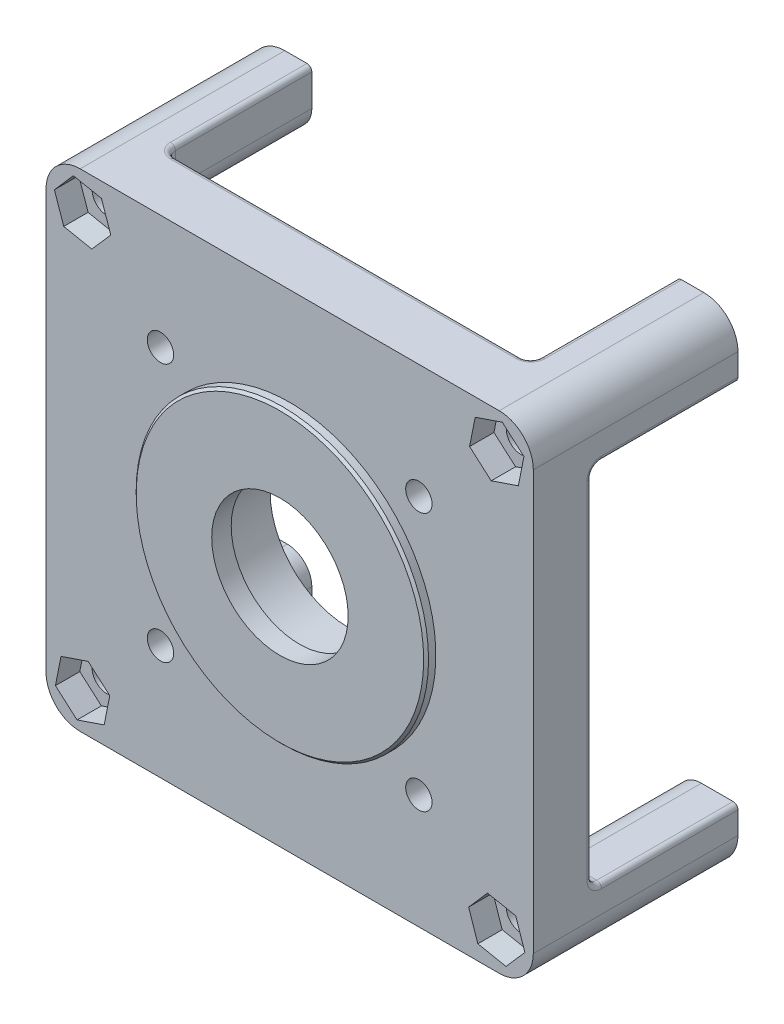
SolidWorks part; units mm, degrees
note: '?' marks a value the reader was unsure of.
ref_plane "Front Plane" through (0, 0, 0) normal (0, 0, 1) x (1, 0, 0)
ref_plane "Top Plane" through (0, 0, 0) normal (0, 1, 0) x (1, 0, 0)
ref_plane "Right Plane" through (0, 0, 0) normal (1, 0, 0) x (0, 0, -1)
ref_axis "Shaft Axis" through (0, 0, -0.635) along (0, 0, 1)?
sketch "Sketch2" plane through (0, 0, 0) normal (0, 0, 1) x (1, 0, 0)
  line L1 (-50, -50) -> (50, -50)
  line L2 (-50, -50) -> (-50, 50)
  line L3 (-50, 50) -> (50, 50)
  line L4 (50, -50) -> (50, 50)
  line L5 (-50, -50) -> (50, 50) construction
  line L6 (-50, 50) -> (50, -50) construction
  point P0 (0, 0)
  dimension "D1" = 100
extrude "Boss-Extrude1" add sketch "Sketch2" along normal blind 12
sketch "Sketch3" plane through (0, 0, 0) normal (0, 0, -1) x (-1, 0, 0)
  circle A0 centre (0, 0) radius 16
  dimension "D1" = 32
extrude "Cut-Extrude1" cut sketch "Sketch3" against normal blind 10
sketch "Sketch14" plane through (0, 0, 12) normal (0, 0, 1) x (1, 0, 0)
  circle A0 centre (0, 0) radius 65
  dimension "D1" = 130
extrude "Cut-Extrude2" [suppressed] cut sketch "Sketch14" against normal blind 2 flip side to cut
hole_wizard "7/16 Clearance Hole1" [suppressed] positions "Sketch7" profile "Sketch8" hole size "7/16" standard "ANSI Inch"
sketch "Sketch7" [suppressed] plane through (0, 0, 10.7) normal (0, 0, 1) x (1, 0, 0)
  line L1 (-58.7375, -58.7375) -> (58.7375, -58.7375) construction
  line L2 (-58.7375, -58.7375) -> (-58.7375, 58.7375) construction
  line L3 (-58.7375, 58.7375) -> (58.7375, 58.7375) construction
  line L4 (58.7375, -58.7375) -> (58.7375, 58.7375) construction
  line L5 (-58.7375, -58.7375) -> (58.7375, 58.7375) construction
  line L6 (-58.7375, 58.7375) -> (58.7375, -58.7375) construction
  line L7 (-76.2, 76.2) -> (76.2, -76.2) construction
  line L8 (76.2, -76.2) -> (76.2, 76.2) construction
  line L9 (76.2, 76.2) -> (-76.2, -76.2) construction
  point P2 (58.7375, 58.7375)
  point P35 (-58.7375, -58.7375)
  point P36 (-58.7375, 58.7375)
  point P37 (58.7375, -58.7375)
  dimension "D1" = 117.475
sketch "Sketch8" plane through (58.7375, 58.7375, 10.7) normal (1, 0, 0) x (0, -1, 0)
  line L0 (0, 0) -> (0, 10.7)
  line L1 (0, 10.7) -> (6.1519, 10.7)
  line L2 (6.1519, 10.7) -> (6.1519, 0)
  line L5 (6.1519, 0) -> (0, 0)
  line L11 (0, -6.35) -> (0, 107.95) construction
  dimension "Thru Hole Dia." = 12.3038
  dimension "Thru Hole Depth" = 10.7
hole_wizard "M6 Clearance Hole1" positions "Sketch13" profile "Sketch12" hole size "M6" standard "ANSI Metric" end condition through all
sketch "Sketch13" plane through (0, 0, 12) normal (0, 0, -1) x (-1, 0, 0)
  line L1 (-42.5, -42.5) -> (42.5, -42.5) construction
  line L2 (-42.5, -42.5) -> (-42.5, 42.5) construction
  line L3 (-42.5, 42.5) -> (42.5, 42.5) construction
  line L4 (42.5, -42.5) -> (42.5, 42.5) construction
  line L5 (-42.5, -42.5) -> (42.5, 42.5) construction
  line L6 (-42.5, 42.5) -> (42.5, -42.5) construction
  line L22 (50, -50) -> (50, 50)
  line L24 (50, 50) -> (-50, -50) construction
  line L26 (-50, 50) -> (50, -50) construction
  line L43 (-50, 50) -> (-50, -50)
  line L44 (-50, 50) -> (-50, -50)
  line L45 (50, 50) -> (-50, 50)
  line L46 (50, 50) -> (-50, 50)
  line L47 (50, -50) -> (50, 50)
  line L48 (50, -50) -> (50, 50)
  line L49 (-50, -50) -> (50, -50)
  line L50 (-50, -50) -> (50, -50)
  point P2 (42.5, 42.5)
  point P61 (-42.5, -42.5)
  point P62 (-42.5, 42.5)
  point P63 (42.5, -42.5)
  dimension "D1" = 85
  dimension "D2" = 0
sketch "Sketch12" plane through (-42.5, 42.5, 12) normal (1, 0, 0) x (0, -1, 0)
  line L0 (0, 0) -> (0, 12)
  line L1 (0, 12) -> (3.05, 12)
  line L2 (3.05, 12) -> (3.05, 0)
  line L5 (3.05, 0) -> (0, 0)
  line L11 (0, -6.35) -> (0, 107.95) construction
  dimension "Thru Hole Dia." = 6.1
  dimension "Thru Hole Depth" = 12
sketch "Sketch17" plane through (0, 0, 0) normal (0, 0, -1) x (-1, 0, 0)
  line L0 (-37.45, 42.5) -> (-37.45, 50)
  line L1 (-50, 50) -> (50, 50) construction
  line L2 (-37.45, 50) -> (-50, 50)
  line L3 (-50, 50) -> (-50, 37.45)
  line L4 (-50, -50) -> (-50, 50) construction
  line L5 (-50, 37.45) -> (-42.5, 37.45)
  arc A0 (-42.5, 37.45) -> (-37.45, 42.5) centre (-42.5, 42.5) ccw
  circle A1 centre (-42.5, 42.5) radius 3.05 construction
  circle A2 centre (-42.5, 42.5) radius 3.05
  dimension "D1" = 2
extrude "Boss-Extrude2" add sketch "Sketch17" along normal blind 30
pattern_circular "CirPattern1" count 4 over 360 about axis through (0, 0, 0) along (0, 0, 1) of "Boss-Extrude2"
sketch "Sketch18" plane through (0, 0, 0) normal (0, 0, -1) x (-1, 0, 0)
  circle A0 centre (0, 0) radius 14
  dimension "D1" = 28
extrude "Cut-Extrude3" cut sketch "Sketch18" against normal through all
fillet "Fillet1" radius 2 12 edges at (38.9291, 38.9291, 0) (-38.9291, 38.9291, 0) (-38.9291, -38.9291, 0) (38.9291, -38.9291, 0) (-37.45, 46.25, 0) (-46.25, 37.45, 0) (-46.25, -37.45, 0) (-37.45, -46.25, 0) (37.45, -46.25, 0) (46.25, -37.45, 0) (46.25, 37.45, 0) (37.45, 46.25, 0)
fillet "Fillet2" radius 7 4 edges at (-50, -50, -9) (50, -50, -9) (50, 50, -9) (-50, 50, -9)
sketch "Sketch24" plane through (0, 0, 12) normal (0, 0, 1) x (1, 0, 0)
  line L1 (-44.4006, 48.0738) -> (-48.2774, 43.6409)
  line L2 (-48.2774, 43.6409) -> (-46.3768, 38.0671)
  line L3 (-46.3768, 38.0671) -> (-40.5994, 36.9262)
  line L4 (-40.5994, 36.9262) -> (-36.7226, 41.3591)
  line L5 (-36.7226, 41.3591) -> (-38.6232, 46.9329)
  line L6 (-38.6232, 46.9329) -> (-44.4006, 48.0738)
  circle A0 centre (-42.5, 42.5) radius 5.1 construction
  dimension "D1" = 10.2
extrude "Cut-Extrude6" cut sketch "Sketch24" against normal blind 5
pattern_circular "CirPattern2" count 4 over 360 about axis through (0, 0, 0) along (0, 0, 1) of "Cut-Extrude6"
sketch "Sketch25" plane through (0, 0, 12) normal (0, 0, 1) x (1, 0, 0)
  circle A0 centre (0, 0) radius 14
  circle A1 centre (0, 0) radius 30
  circle A2 centre (0, 0) radius 14 construction
  dimension "D1" = 60
extrude "Boss-Extrude3" add sketch "Sketch25" along normal blind 2
sketch "Sketch26" plane through (0, 0, 12) normal (0, 0, 1) x (1, 0, 0)
  line L1 (-26.5165, 26.5165) -> (26.5165, 26.5165)
  line L2 (-26.5165, 26.5165) -> (-26.5165, -26.5165)
  line L3 (-26.5165, -26.5165) -> (26.5165, -26.5165)
  line L4 (26.5165, 26.5165) -> (26.5165, -26.5165)
  line L5 (-26.5165, 26.5165) -> (26.5165, -26.5165) construction
  line L6 (-26.5165, -26.5165) -> (26.5165, 26.5165) construction
  point P0 (0, 0)
  dimension "D1" = 75
  dimension "D2" = 45
hole_wizard "#3 (0.213) Diameter Hole1" positions "3DSketch1" profile "Sketch27" hole size "#3" standard "ANSI Inch" end condition up to next
sketch3d "3DSketch1"
  point P0 (26.5165, 26.5165, 12)
  point P3 (-26.5165, 26.5165, 12)
  point P6 (-26.5165, -26.5165, 12)
  point P9 (26.5165, -26.5165, 12)
sketch "Sketch27" plane through (26.5165, 26.5165, 12) normal (1, 0, 0) x (0, -1, 0)
  line L0 (0, 0) -> (0, 12)
  line L1 (0, 12) -> (2.7051, 12)
  line L2 (2.7051, 12) -> (2.7051, 0)
  line L5 (2.7051, 0) -> (0, 0)
  line L11 (0, -6.35) -> (0, 107.95) construction
  dimension "Thru Hole Dia." = 5.4102
  dimension "Thru Hole Depth" = 12
chamfer "Chamfer1" distance 0.5 angle 45 1 edges at (30, 0, 14)
fillet "Fillet3" radius 1 20 edges at (50, 0, 0) (0, -50, 0) (-50, 0, 0) (0, 50, 0) (-36.8642, 50, -0.5858) (-50, 36.8642, -0.5858) (-50, -36.8642, -0.5858) (-36.8642, -50, -0.5858) (36.8642, -50, -0.5858) (50, -36.8642, -0.5858) (50, 36.8642, -0.5858) (36.8642, 50, -0.5858) (37.45, 50, -16) (50, 37.45, -16) (-50, 37.45, -16) (-37.45, 50, -16) (-37.45, -50, -16) (-50, -37.45, -16) (50, -37.45, -16) (37.45, -50, -16)
